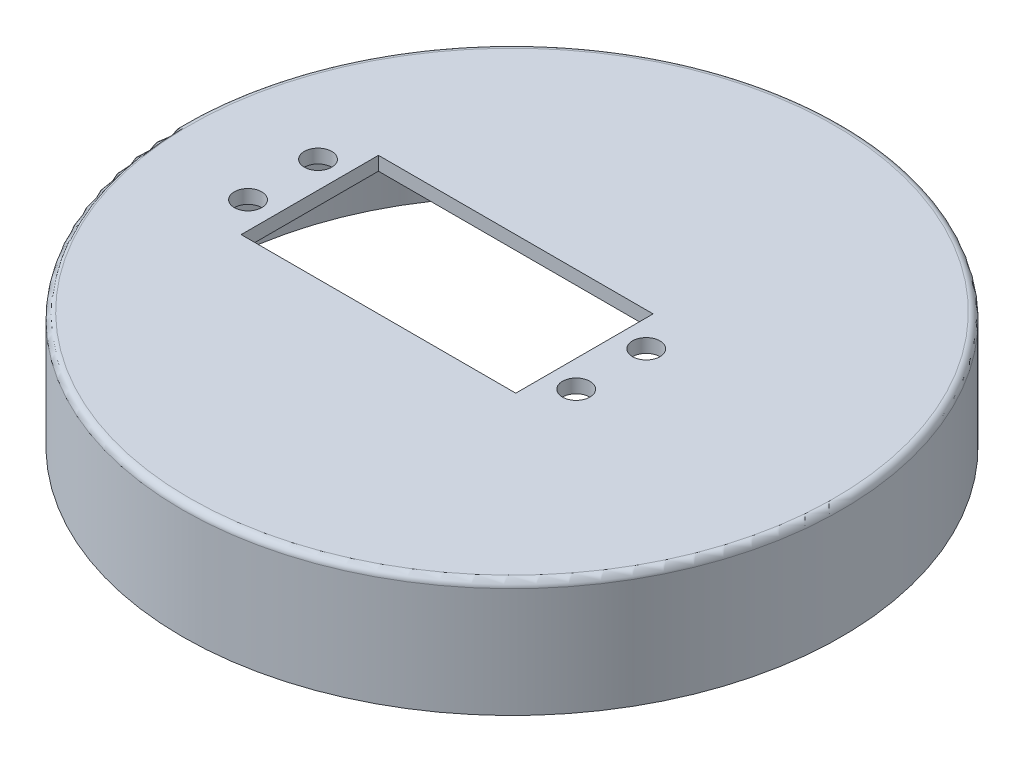
SolidWorks part; units mm, degrees
ref_plane "Front Plane" through (0, 0, 0) normal (0, 0, 1) x (1, 0, 0)
ref_plane "Top Plane" through (0, 0, 0) normal (0, 1, 0) x (1, 0, 0)
ref_plane "Right Plane" through (0, 0, 0) normal (1, 0, 0) x (0, 0, -1)
sketch "Sketch1" plane through (0, 0, 0) normal (0, 1, 0) x (1, 0, 0)
  line L1 (-62.5, -62.5) -> (62.5, -62.5)
  line L2 (-62.5, -62.5) -> (-62.5, 62.5)
  line L3 (-62.5, 62.5) -> (62.5, 62.5)
  line L4 (62.5, -62.5) -> (62.5, 62.5)
  line L5 (-62.5, -62.5) -> (62.5, 62.5) construction
  line L6 (-62.5, 62.5) -> (62.5, -62.5) construction
  circle A0 centre (0, 0) radius 44.5
  circle A1 centre (0, 0) radius 48
  dimension "D1" = 89
  dimension "D3" = 125
  dimension "D4" = 125
  dimension "D2" = 3.5
extrude "Boss-Extrude3" add sketch "Sketch1" against normal blind 15 contours A0 | A1 region at (0, 0, 0)
extrude "Boss-Extrude4" add sketch "Sketch1<5>" along normal blind 2 contours A1 A0 | A0 region at (0, 0, 0) region at (-46.6424, 0, 0)
sketch "Sketch1<5>" plane through (0, 0, 0) normal (0, 1, 0) x (1, 0, 0) same geometry as "Sketch1"
fillet "Fillet1" radius 1 2 edges at (0, 0, 44.5) (0, 2, 48)
sketch "Sketch3" plane through (0, 2, 0) normal (0, 1, 0) x (1, 0, 0)
  line L0 (0, 0) -> (-29.45, 0)
  line L1 (-29.45, 0) -> (-29.45, -10)
  line L3 (-29.45, -10) -> (10.55, -10)
  line L4 (-29.45, -10) -> (-29.45, 10)
  line L5 (-29.45, 10) -> (10.55, 10)
  line L6 (10.55, -10) -> (10.55, 10)
  circle A0 centre (0, 0) radius 3.7105
  dimension "D1" = 29.45
  dimension "D2" = 10
  dimension "D3" = 40
  dimension "D4" = 20
extrude "Cut-Extrude1" cut sketch "Sketch3" against normal blind 30 contours A0 L1 L3 L6 L5 L4 | A0 region at (-29.0028, 2, -5) region at (0, 2, -3.6055)
sketch "Sketch4" plane through (0, 2, 0) normal (0, 1, 0) x (1, 0, 0)
  line L0 (-29.45, -10) -> (10.55, -10) construction
  line L1 (10.55, -10) -> (10.55, 10) construction
  line L2 (10.55, 0) -> (-29.45, 0) construction
  line L3 (-29.45, 10) -> (-29.45, -10) construction
  line L4 (-9.45, 0) -> (-9.45, 13.1126) construction
  circle A0 centre (-33.3489, -5.0986) radius 2
  circle A1 centre (14.4489, -5.0986) radius 2
  circle A2 centre (14.4489, 5.0986) radius 2
  circle A3 centre (-33.3489, 5.0986) radius 2
extrude "Cut-Extrude2" cut sketch "Sketch4" against normal blind 10 contours A1 | A2 | A0 | A3 region at (-33.3489, 2, 5.0986) region at (14.4489, 2, 5.0986) region at (14.4489, 2, -5.0986) region at (-33.3489, 2, -5.0986)
